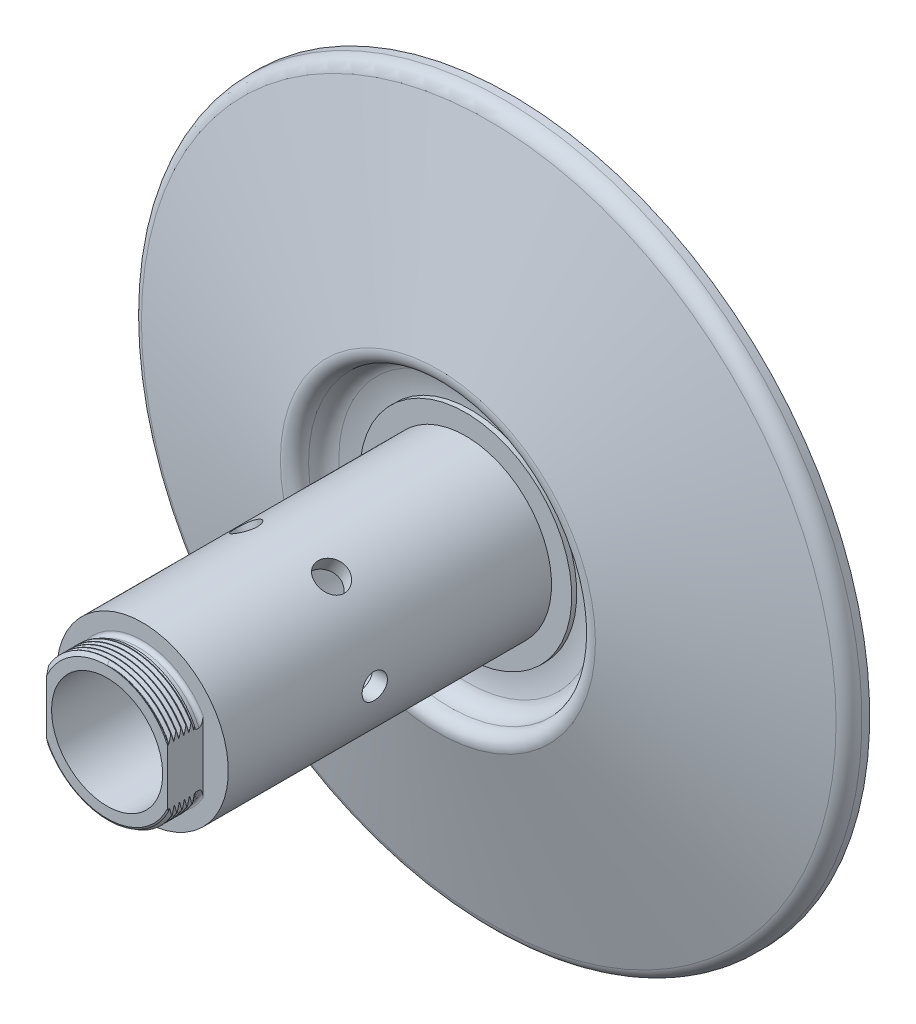
SolidWorks part; units mm, degrees
material "S355JR"
ref_plane "Front" through (0, 0, 0) normal (0, 0, 1) x (1, 0, 0)
ref_plane "Top" through (0, 0, 0) normal (0, 1, 0) x (1, 0, 0)
ref_plane "Right" through (0, 0, 0) normal (1, 0, 0) x (0, 0, -1)
sketch "Sketch1" plane through (0, 0, 0) normal (1, 0, 0) x (0, 0, -1)
  line L0 (0, 0) -> (-8901.9585, 0) construction
  line L1 (-20, 11) -> (-39, 11)
  line L2 (-39, 11) -> (-39, 13.134)
  line L3 (-39, 13.134) -> (-38.5625, 13.8917)
  line L4 (-38.5625, 13.8917) -> (-33.9375, 13.8917)
  line L5 (-33.9375, 13.8917) -> (-33.5, 13.134)
  line L6 (-33.5, 13.134) -> (-32.8, 13.134)
  line L7 (-32, 13.934) -> (-32, 17)
  line L8 (-32, 17) -> (32, 17)
  line L9 (-39.5, 14) -> (-39, 13.134) construction
  line L10 (-39, 13.134) -> (-38.5, 14) construction
  line L11 (-38.5, 14) -> (-39.5, 14) construction
  line L12 (-39.5, 14) -> (-39.5, 13.7835) construction
  line L13 (-39.5, 13.7835) -> (-39.5, 13.567) construction
  line L14 (-39.5, 13.567) -> (-39.5, 13.3505) construction
  line L15 (-39.5, 13.3505) -> (-39.5, 13.134) construction
  line L16 (-39.5, 13.134) -> (-39, 13.134) construction
  line L17 (-39.5, 13.8917) -> (-38.5625, 13.8917) construction
  line L18 (-20, 11) -> (-20, 14)
  line L19 (-20, 14) -> (-13, 14)
  line L20 (-13, 14) -> (-13, 14.7)
  line L21 (-13, 14.7) -> (-11.7, 14.7)
  line L22 (-11.7, 14.7) -> (-11.7, 14)
  line L23 (-11.7, 14) -> (21, 14)
  line L24 (32, 17) -> (32, 21)
  line L25 (32, 21) -> (33, 21)
  line L26 (26.4974, 31.1921) -> (36.5681, 68.7765)
  line L27 (26.4123, 30.545) -> (26.4123, 61.5734) construction
  line L29 (37, 15) -> (37, 19)
  line L30 (38.5, 68.2588) -> (28.4293, 30.6744)
  line L31 (39.4659, 71) -> (41, 71)
  line L32 (41, 71) -> (41, 69)
  line L33 (41, 69) -> (39.4659, 69)
  line L34 (37, 19) -> (40, 19)
  line L35 (37, 15) -> (21, 15)
  line L36 (21, 15) -> (21, 14)
  arc A0 (-32.8, 13.134) -> (-32, 13.934) centre (-32.8, 13.934) ccw
  arc A4 (36.5681, 68.7765) -> (39.4659, 71) centre (39.4659, 68) cw
  arc A5 (28.9158, 30.045) -> (34.5, 24.5) centre (28.9548, 24.5) cw
  arc A6 (34.5, 24.5) -> (35, 24) centre (35, 24.5) ccw
  arc A8 (39.4659, 69) -> (38.5, 68.2588) centre (39.4659, 68) ccw
  arc A9 (40, 19) -> (35, 24) centre (35, 19) ccw
  arc A10 (33, 21) -> (32.3582, 25.4926) centre (16.9548, 21) ccw
  arc A11 (32.3582, 25.4926) -> (28.9299, 28.0451) centre (28.9548, 24.5) ccw
  arc A12 (28.4293, 30.6744) -> (28.9158, 30.045) centre (28.9123, 30.545) ccw
  arc A13 (28.9299, 28.0451) -> (26.4974, 31.1921) centre (28.9123, 30.545) cw
  point P21 (0, 17)
  point P54 (28.2486, 30)
  dimension "D5" = 0.8
  dimension "D15" = 0.5
  dimension "D24" = 3
  dimension "D30" = 2
  dimension "D31" = 0.5
  dimension "D1" = 28
  dimension "D2" = 1
  dimension "D3" = 34
  dimension "D4" = 7
  dimension "D6" = 1.5
  dimension "D7" = 71
  dimension "D8" = 22
  dimension "D9" = 28
  dimension "D10" = 19
  dimension "D11" = 15
  dimension "D12" = 30
  dimension "D13" = 1
  dimension "D14" = 42
  dimension "D16" = 16
  dimension "D17" = 142
  dimension "D18" = 76
  dimension "D19" = 7
  dimension "D20" = 1.3
  dimension "D21" = 29.4
  dimension "D22" = 48
  dimension "D23" = 2
  dimension "D25" = 2.5
  dimension "D26" = 60
  dimension "D27" = 3
  dimension "D28" = 38
  dimension "D29" = 1
revolve "Revolve1" add sketch "Sketch1" angle 360 about L0
sketch "Sketch2" plane through (0, 0, 39) normal (0, 0, 1) x (1, 0, 0)
  circle A0 centre (0, 0) radius 13.8917 construction
  circle A1 centre (0, 0) radius 13.8917
curve "Helix/Spiral1" pitch 1 height 5.5 radius 13.8917 centre (0, 0, 39) axis (0, 0, -1) start towards (0, 1, 0)
sketch "Sketch3" plane through (0, 0, 0) normal (1, 0, 0) x (0, 0, -1)
  line L0 (-39.4375, 13.8917) -> (-39.4375, 14)
  line L1 (-39.5, 13.8917) -> (-38.5625, 13.8917) construction
  line L2 (-39.5, 14) -> (-39, 13.134) construction
  line L3 (-38.5, 14) -> (-39.5, 14) construction
  line L4 (-39.4375, 14) -> (-38.5625, 14)
  line L5 (-38.5625, 14) -> (-38.5625, 13.8917)
  line L6 (-38.5625, 13.8917) -> (-38.9375, 13.2422)
  line L7 (-39, 13.134) -> (-38.5625, 13.8917) construction
  line L8 (-39.0625, 13.2422) -> (-39.4375, 13.8917)
  line L9 (-39.5, 13.2422) -> (-39.0625, 13.2422) construction
  line L10 (-39.5, 13.3505) -> (-39.5, 13.134) construction
  arc A0 (-38.9375, 13.2422) -> (-39.0625, 13.2422) centre (-39, 13.2783) cw
sweep "Cut-Sweep1" cut profiles "Sketch3" path "Helix/Spiral1" align with end faces yes
sketch "Sketch4" plane through (0, 0, 39) normal (0, 0, 1) x (1, 0, 0)
  line L0 (-12, 12.0416) -> (-12, -12.0416)
  line L1 (0, 0) -> (0, 29.4788) construction
  line L2 (12, 12.0416) -> (12, -12.0416)
  arc A0 (-12, 12.0416) -> (-12, -12.0416) centre (0, 0) ccw
  circle A1 centre (0, 0) radius 17 construction
  arc A2 (12, 12.0416) -> (12, -12.0416) centre (0, 0) cw
  dimension "D1" = 24
extrude "Cut-Extrude1" cut sketch "Sketch4" against normal up to surface (7 mm away) up to face at (-13.934, 0, 32)
sketch "Sketch5" plane through (0, 0, 0) normal (1, 0, 0) x (0, 0, -1)
  line L0 (-39, 5.3387) -> (-39, -5.3387) construction
  circle A0 centre (-3, 0) radius 3
  dimension "D1" = 6
  dimension "D2" = 36
extrude "Cut-Extrude2" cut sketch "Sketch5" against normal through all
ref_plane "Plane1" through (0, 0, 0) normal (0.5, -0.866, 0) x (0, 0, -1)
sketch "Sketch6" plane through (0, 0, 0) normal (0.5, -0.866, 0) x (0, 0, -1)
  line L0 (-39, 13.0616) -> (-39, 7.723) construction
  circle A0 centre (-3, 0) radius 2.5
  dimension "D1" = 36
  dimension "D2" = 5
extrude "Cut-Extrude3" cut sketch "Sketch6" against normal through all
pattern_circular "CirPattern1" count 3 over 360 about axis through (0, 0, 0) along (0, 0, -1) of "Cut-Extrude2", "Cut-Extrude3"
